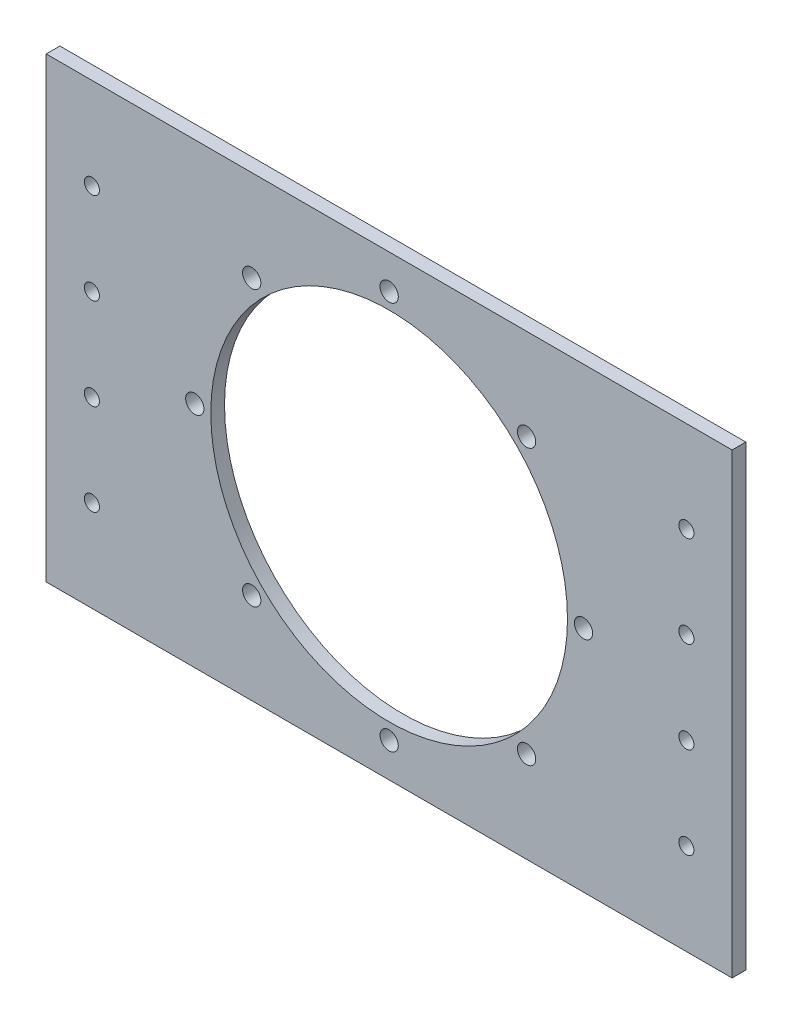
SolidWorks part; units mm, degrees
ref_plane "前视基准面" through (0, 0, 0) normal (0, 0, 1) x (1, 0, 0)
ref_plane "上视基准面" through (0, 0, 0) normal (0, 1, 0) x (1, 0, 0)
ref_plane "右视基准面" through (0, 0, 0) normal (1, 0, 0) x (0, 0, -1)
other "Configuration Table"
sketch "草图1" plane through (0, 0, 0) normal (0, 0, 1) x (1, 0, 0)
  line L0 (0, 0) -> (0, 90.0014) construction
  line L5 (-75, 50) -> (75, 50)
  line L6 (-75, 50) -> (-75, -50)
  line L7 (-75, -50) -> (75, -50)
  line L8 (75, 50) -> (75, -50)
  line L9 (-75, 50) -> (75, -50) construction
  line L10 (-75, -50) -> (75, 50) construction
  line L11 (-65, 50) -> (-65, -50) construction
  line L12 (65, 50) -> (65, -50) construction
  circle A10 centre (0, 0) radius 39
  circle A11 centre (0, 0) radius 42.5 construction
  circle A13 centre (42.5, 0) radius 2
  circle A14 centre (30.052, -30.052) radius 2
  circle A15 centre (0, -42.5) radius 2
  circle A16 centre (-30.052, -30.052) radius 2
  circle A17 centre (-42.5, 0) radius 2
  circle A18 centre (-30.052, 30.052) radius 2
  circle A19 centre (0, 42.5) radius 2
  circle A20 centre (30.052, 30.052) radius 2
  circle A21 centre (-65, 30) radius 1.65
  circle A22 centre (-65, 10) radius 1.65
  circle A23 centre (-65, -10) radius 1.65
  circle A24 centre (-65, -30) radius 1.65
  circle A25 centre (65, -30) radius 1.65
  circle A26 centre (65, -10) radius 1.65
  circle A27 centre (65, 10) radius 1.65
  circle A28 centre (65, 30) radius 1.65
  circle A29 centre (0, 0) radius 44.5 construction
  circle A30 centre (0, 0) radius 44.5 construction
  point P22 (0, 0)
  dimension "D2" = 78
  dimension "D4" = 4
  dimension "D3" = 85
  dimension "D10" = 3.3
  dimension "D11" = 3.3
  dimension "D12" = 3.3
  dimension "D13" = 3.3
  dimension "D17" = 89
  dimension "D18" = 89
  dimension "D6" = 100
  dimension "D7" = 150
  dimension "D8" = 10
  dimension "D9" = 20
  dimension "D14" = 20
  dimension "D15" = 20
  dimension "D16" = 20
  dimension "D5" = 8
extrude "凸台-拉伸1" add sketch "草图1" along normal blind 3
